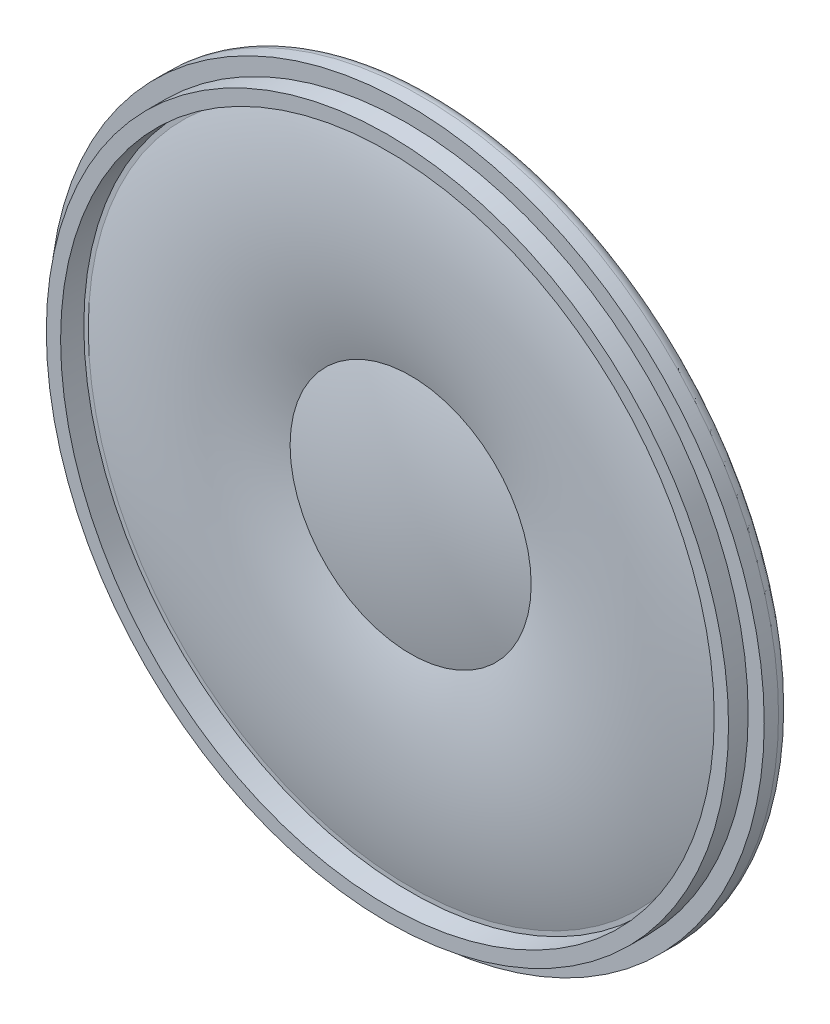
SolidWorks part; units mm, degrees
material "ABS"
ref_plane "Спереди" through (0, 0, 0) normal (0, 0, 1) x (1, 0, 0)
ref_plane "Сверху" through (0, 0, 0) normal (0, 1, 0) x (1, 0, 0)
ref_plane "Справа" through (0, 0, 0) normal (1, 0, 0) x (0, 0, -1)
ref_axis "Ось1" through (0, 0, 50) along (0, 0, -1)
sketch "Эскиз1" plane through (0, 0, 0) normal (0, 1, 0) x (1, 0, 0)
  line L0 (0, 0) -> (7.625, 0)
  line L1 (8.125, -0.5) -> (8.125, -1.7)
  line L2 (8.125, -1.7) -> (16.8298, -1.7)
  line L4 (18.1, -3.2) -> (19.3, -3.2)
  line L5 (20, -3.9) -> (20, -4.7)
  line L6 (20, -4.7) -> (19.1, -4.7)
  line L7 (19.1, -4.7) -> (19.1, -5.8)
  line L8 (19.1, -5.8) -> (18.3, -5.8)
  line L9 (18.3, -5.8) -> (18.3, -4.5)
  line L10 (18.3, -4.5) -> (18.05, -4.5)
  line L11 (0, 0) -> (0, -5.3)
  line L12 (0, -5.3) -> (11.3788, -5.3) construction
  line L13 (0, 0) -> (0, -8.5626) construction
  line L14 (17.436, -2.05) -> (18.1, -3.2)
  arc A0 (0, -5.3) -> (6.75, -4.5) centre (0, 23.5766) ccw
  arc A1 (6.75, -4.5) -> (18.05, -4.5) centre (12.4, 15.0516) ccw
  arc A2 (17.436, -2.05) -> (16.8298, -1.7) centre (16.8298, -2.4) ccw
  arc A3 (20, -3.9) -> (19.3, -3.2) centre (19.3, -3.9) ccw
  arc A4 (8.125, -0.5) -> (7.625, 0) centre (7.625, -0.5) ccw
  point P19 (18.132, -1.7924)
  point P22 (20, -3.2)
  point P25 (8.125, 0)
  dimension "D12" = 0.7
  dimension "D15" = 38.2
  dimension "D16" = 0.7
  dimension "D17" = 0.5
  dimension "D2" = 16.25
  dimension "D3" = 1.7
  dimension "D4" = 1.5
  dimension "D5" = 60
  dimension "D6" = 1.5
  dimension "D7" = 1.1
  dimension "D8" = 36.1
  dimension "D9" = 0.8
  dimension "D10" = 1.3
  dimension "D11" = 5.8
  dimension "D13" = 13.5
  dimension "D14" = 5.3
  dimension "D18" = 40
  dimension "D19" = 36.2
revolve "Повернуть2" add sketch "Эскиз1" angle 360 about L11
sketch "Эскиз2" plane through (0, 0, 1.7) normal (0, 0, -1) x (-1, 0, 0)
  line L0 (7.5, -7.8125) -> (7.5, -15.0663)
  line L1 (-7.5, -7.8125) -> (-7.5, -15.0663)
  line L2 (0, 0) -> (7.5, -7.8125) construction
  line L3 (0, 0) -> (-7.5, -7.8125) construction
  line L4 (0, -10.8298) -> (0, -16.8298) construction
  arc A0 (-7.5, -7.8125) -> (7.5, -7.8125) centre (0, 0) ccw
  arc A1 (-7.5, -15.0663) -> (7.5, -15.0663) centre (0, 0) ccw
  circle A4 centre (0, 0) radius 16.8298 construction
  dimension "D1" = 6
  dimension "D2" = 15
extrude "Бобышка-Вытянуть2" add sketch "Эскиз2" along normal blind 0.4
sketch "Эскиз3" plane through (0, 0, 0) normal (0, 0, -1) x (-1, 0, 0)
  text T0 "8Ω 2W\r\n" font "Arial" height 3
  text T1 "−  +" font "Arial" height 4
extrude "Бобышка-Вытянуть3" add sketch "Эскиз3" along normal blind 0.01
